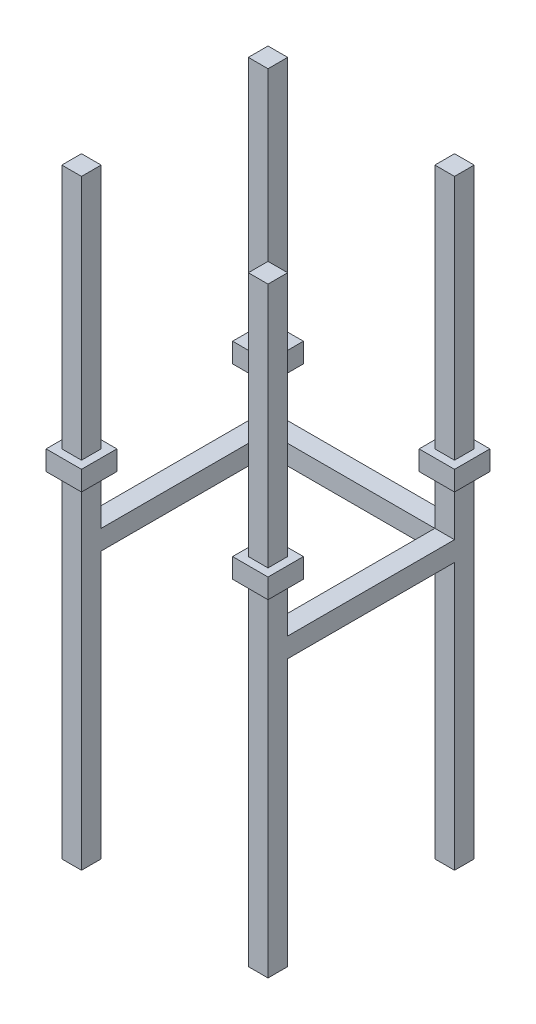
SolidWorks part; units mm, degrees
ref_plane "Alzado" through (0, 0, 0) normal (0, 0, 1) x (1, 0, 0)
ref_plane "Planta" through (0, 0, 0) normal (0, 1, 0) x (1, 0, 0)
ref_plane "Vista lateral" through (0, 0, 0) normal (1, 0, 0) x (0, 0, -1)
sketch "Croquis1" plane through (0, 0, 0) normal (0, 1, 0) x (1, 0, 0)
  line L0 (0, 300) -> (0, -300) construction
  line L1 (-212.132, 212.132) -> (212.132, 212.132) construction
  line L2 (-212.132, 212.132) -> (-212.132, -212.132) construction
  line L3 (-212.132, -212.132) -> (212.132, -212.132) construction
  line L4 (212.132, 212.132) -> (212.132, -212.132) construction
  line L5 (-212.132, 212.132) -> (212.132, -212.132) construction
  line L6 (-212.132, -212.132) -> (212.132, 212.132) construction
  line L7 (-212.132, 212.132) -> (-262.132, 212.132)
  line L8 (-212.132, 212.132) -> (-212.132, 262.132)
  line L9 (-212.132, 262.132) -> (-262.132, 262.132)
  line L10 (-262.132, 212.132) -> (-262.132, 262.132)
  line L11 (262.132, 212.132) -> (262.132, 262.132)
  line L12 (212.132, 262.132) -> (262.132, 262.132)
  line L13 (212.132, 212.132) -> (212.132, 262.132)
  line L14 (212.132, 212.132) -> (262.132, 212.132)
  line L15 (-300, 0) -> (300, 0) construction
  line L16 (-262.132, -212.132) -> (-262.132, -262.132)
  line L17 (-212.132, -262.132) -> (-262.132, -262.132)
  line L18 (-212.132, -212.132) -> (-212.132, -262.132)
  line L19 (-212.132, -212.132) -> (-262.132, -212.132)
  line L20 (212.132, -212.132) -> (262.132, -212.132)
  line L21 (212.132, -212.132) -> (212.132, -262.132)
  line L22 (212.132, -262.132) -> (262.132, -262.132)
  line L23 (262.132, -212.132) -> (262.132, -262.132)
  circle A0 centre (0, 0) radius 300 construction
  dimension "D1" = 600
  dimension "D2" = 50
  dimension "D3" = 50
extrude "Saliente-Extruir1" add sketch "Croquis1" against normal blind 625
sketch "Croquis2" plane through (0, -625, 0) normal (0, -1, 0) x (1, 0, 0)
  line L0 (0, 307.8427) -> (0, -307.8427) construction
  line L1 (-282.132, 282.132) -> (-192.132, 282.132)
  line L2 (-282.132, 282.132) -> (-282.132, 192.132)
  line L3 (-282.132, 192.132) -> (-192.132, 192.132)
  line L4 (-192.132, 282.132) -> (-192.132, 192.132)
  line L5 (-282.132, 282.132) -> (-192.132, 192.132) construction
  line L6 (-282.132, 192.132) -> (-192.132, 282.132) construction
  line L7 (-307.361, 0) -> (310.4962, 0) construction
  line L8 (282.132, 192.132) -> (192.132, 282.132) construction
  line L9 (282.132, 282.132) -> (192.132, 192.132) construction
  line L10 (192.132, 282.132) -> (192.132, 192.132)
  line L11 (282.132, 192.132) -> (192.132, 192.132)
  line L12 (282.132, 282.132) -> (282.132, 192.132)
  line L13 (282.132, 282.132) -> (192.132, 282.132)
  line L14 (282.132, -282.132) -> (192.132, -192.132) construction
  line L15 (282.132, -192.132) -> (192.132, -282.132) construction
  line L16 (282.132, -282.132) -> (192.132, -282.132)
  line L17 (282.132, -282.132) -> (282.132, -192.132)
  line L18 (282.132, -192.132) -> (192.132, -192.132)
  line L19 (192.132, -282.132) -> (192.132, -192.132)
  line L20 (-282.132, -192.132) -> (-192.132, -282.132) construction
  line L21 (-282.132, -282.132) -> (-192.132, -192.132) construction
  line L22 (-192.132, -282.132) -> (-192.132, -192.132)
  line L23 (-282.132, -192.132) -> (-192.132, -192.132)
  line L24 (-282.132, -282.132) -> (-282.132, -192.132)
  line L25 (-282.132, -282.132) -> (-192.132, -282.132)
  line L27 (212.132, 212.132) -> (-212.132, 212.132) construction
  line L28 (212.132, 212.132) -> (212.132, -212.132) construction
  line L29 (212.132, -212.132) -> (-212.132, -212.132) construction
  line L30 (-212.132, 212.132) -> (-212.132, -212.132) construction
  line L31 (212.132, 212.132) -> (-212.132, -212.132) construction
  line L32 (212.132, -212.132) -> (-212.132, 212.132) construction
  line L33 (237.132, -237.132) -> (-237.132, -237.132) construction
  line L34 (237.132, -237.132) -> (237.132, 237.132) construction
  line L35 (237.132, 237.132) -> (-237.132, 237.132) construction
  line L36 (-237.132, -237.132) -> (-237.132, 237.132) construction
  circle A0 centre (0, 0) radius 300 construction
  point P0 (-237.132, 237.132)
  point P14 (237.132, 237.132)
  point P19 (237.132, -237.132)
  point P24 (-237.132, -237.132)
  point P27 (0, 0)
  point P37 (-237.132, 237.132)
  dimension "D3" = 600
  dimension "D1" = 90
  dimension "D2" = 90
extrude "Saliente-Extruir2" add sketch "Croquis2" along normal blind 50
sketch "Croquis4" plane through (0, -675, 0) normal (0, -1, 0) x (1, 0, 0)
  line L0 (0, -282.8427) -> (0, 282.8427) construction
  line L1 (-212.132, 212.132) -> (-262.132, 212.132)
  line L2 (-212.132, 212.132) -> (-212.132, 262.132)
  line L3 (-212.132, 262.132) -> (-262.132, 262.132)
  line L4 (-262.132, 212.132) -> (-262.132, 262.132)
  line L5 (-275.9995, 0) -> (282.8427, 0) construction
  line L6 (-262.132, -212.132) -> (-262.132, -262.132)
  line L7 (-212.132, -262.132) -> (-262.132, -262.132)
  line L8 (-212.132, -212.132) -> (-212.132, -262.132)
  line L9 (-212.132, -212.132) -> (-262.132, -212.132)
  line L10 (262.132, 212.132) -> (262.132, 262.132)
  line L11 (212.132, 262.132) -> (262.132, 262.132)
  line L12 (212.132, 212.132) -> (212.132, 262.132)
  line L13 (212.132, 212.132) -> (262.132, 212.132)
  line L14 (212.132, -212.132) -> (262.132, -212.132)
  line L15 (212.132, -212.132) -> (212.132, -262.132)
  line L16 (212.132, -262.132) -> (262.132, -262.132)
  line L17 (262.132, -212.132) -> (262.132, -262.132)
extrude "Saliente-Extruir3" add sketch "Croquis4" along normal blind 853
ref_plane "Plano1" through (0, -800, 0) normal (0, 1, 0) x (1, 0, 0)
sketch "Croquis6" plane through (0, -800, 0) normal (0, 1, 0) x (1, 0, 0)
  line L21 (262.132, -262.132) -> (262.132, -212.132) construction
  line L30 (-262.132, 262.132) -> (262.132, 262.132)
  line L31 (-262.132, 262.132) -> (-262.132, -262.132)
  line L32 (-262.132, -262.132) -> (-212.132, -262.132)
  line L33 (262.132, 262.132) -> (262.132, -262.132)
  line L34 (262.132, -262.132) -> (262.132, -212.132) construction
  line L35 (-212.132, -212.132) -> (-212.132, -262.132)
  line L36 (-212.132, 212.132) -> (212.132, 212.132)
  line L37 (-212.132, 212.132) -> (-212.132, -212.132)
  line L39 (212.132, 212.132) -> (212.132, -212.132)
  line L40 (212.132, -212.132) -> (212.132, -262.132)
  line L41 (212.132, -212.132) -> (212.132, -262.132) construction
  line L42 (212.132, -262.132) -> (262.132, -262.132)
extrude "Saliente-Extruir4" add sketch "Croquis6" against normal blind 50
